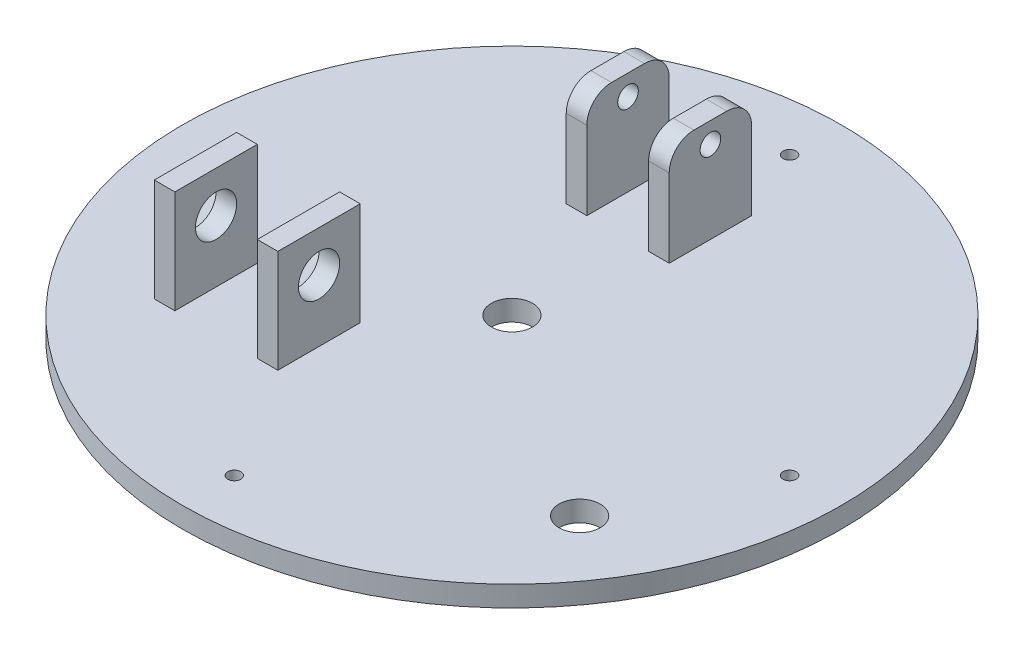
SolidWorks part; units mm, degrees
material "6061 Alloy"
ref_plane "Front Plane" through (0, 0, 0) normal (0, 0, 1) x (1, 0, 0)
ref_plane "Top Plane" through (0, 0, 0) normal (0, 1, 0) x (1, 0, 0)
ref_plane "Right Plane" through (0, 0, 0) normal (1, 0, 0) x (0, 0, -1)
sketch "Sketch1" plane through (0, 0, 0) normal (0, 1, 0) x (1, 0, 0)
  circle A0 centre (0, 0) radius 101.6
  dimension "D1" = 203.2
extrude "Boss-Extrude1" add sketch "Sketch1" along normal blind 6.35
sketch "Sketch2" plane through (0, 0, 0) normal (0, -1, 0) x (1, 0, 0)
  circle A0 centre (0, 0) radius 6.35
  dimension "D1" = 12.7
extrude "Cut-Extrude1" cut sketch "Sketch2" against normal through all
sketch "Sketch3" plane through (0, 6.35, 0) normal (0, 1, 0) x (1, 0, 0)
  line L0 (-53.1127, -38.1) -> (-27.7127, -38.1) construction
  line L1 (-59.4627, -25.4) -> (-53.1127, -25.4)
  line L2 (-59.4627, -25.4) -> (-59.4627, -50.8)
  line L3 (-59.4627, -50.8) -> (-53.1127, -50.8)
  line L4 (-53.1127, -25.4) -> (-53.1127, -50.8)
  line L5 (-27.7127, -25.4) -> (-21.3627, -25.4)
  line L6 (-27.7127, -25.4) -> (-27.7127, -50.8)
  line L7 (-27.7127, -50.8) -> (-21.3627, -50.8)
  line L8 (-21.3627, -25.4) -> (-21.3627, -50.8)
  point P10 (-40.4127, -38.1)
  dimension "D1" = 40.4127
  dimension "D2" = 6.35
  dimension "D3" = 38.1
  dimension "D4" = 25.4
  dimension "D5" = 25.4
extrude "Boss-Extrude2" add sketch "Sketch3" along normal blind 31.75
sketch "Sketch4" plane through (-21.3627, 0, 0) normal (1, 0, 0) x (0, 0, -1)
  line L0 (-38.1, 38.1) -> (-38.1, 25.4) construction
  line L1 (-50.8, 38.1) -> (-25.4, 38.1) construction
  circle A0 centre (-38.1, 25.4) radius 6.35
  dimension "D1" = 12.7
  dimension "D2" = 12.7
extrude "Cut-Extrude2" cut sketch "Sketch4" against normal up to surface (38.1 mm away) up to face at (-59.4627, 22.225, 38.1)
sketch "Sketch5" plane through (0, 6.35, 0) normal (0, 1, 0) x (1, 0, 0)
  line L0 (-15.0127, 50.8) -> (4.0373, 50.8) construction
  line L2 (-21.3627, 38.1) -> (-15.0127, 38.1)
  line L3 (-21.3627, 38.1) -> (-21.3627, 63.5)
  line L4 (-21.3627, 63.5) -> (-15.0127, 63.5)
  line L5 (-15.0127, 38.1) -> (-15.0127, 63.5)
  line L6 (4.0373, 63.5) -> (10.3873, 63.5)
  line L7 (4.0373, 63.5) -> (4.0373, 38.1)
  line L8 (4.0373, 38.1) -> (10.3873, 38.1)
  line L9 (10.3873, 63.5) -> (10.3873, 38.1)
  point P10 (-5.4877, 50.8)
  dimension "D1" = 25.4
  dimension "D2" = 6.35
  dimension "D3" = 19.05
  dimension "D4" = 34.925
  dimension "D5" = 88.9
extrude "Boss-Extrude3" add sketch "Sketch5" along normal blind 31.75
sketch "Sketch6" plane through (-21.3627, 0, 0) normal (-1, 0, 0) x (0, 0, 1)
  line L0 (-50.8, 38.1) -> (-50.8, 31.75) construction
  line L1 (-63.5, 38.1) -> (-38.1, 38.1) construction
  circle A0 centre (-50.8, 31.75) radius 3.175
  dimension "D1" = 6.35
  dimension "D2" = 6.35
extrude "Cut-Extrude3" cut sketch "Sketch6" against normal up to surface (31.75 mm away) up to face at (10.3873, 22.225, -50.8)
hole_wizard "#10-32 Tapped Hole1" positions "Sketch8" profile "Sketch7" tap size "#10-32" standard "ANSI Inch"
sketch "Sketch8" plane through (0, 0, 0) normal (0, -1, 0) x (-1, 0, 0)
  line L1 (85.5998, 0) -> (0, 85.5998)
  line L2 (85.5998, 0) -> (0, -85.5998)
  line L3 (0, 85.5998) -> (-85.5998, 0)
  line L4 (0, -85.5998) -> (-85.5998, 0)
  line L5 (85.5998, 0) -> (-85.5998, 0) construction
  line L6 (0, 85.5998) -> (0, -85.5998) construction
  point P252 (0, 0)
  point P331 (0, -85.5998)
  point P333 (-85.5998, 0)
  point P335 (0, 85.5998)
  point P337 (85.5998, 0)
  dimension "D1" = 121.0564
sketch "Sketch7" plane through (0, 0, 0) normal (1, 0, 0) x (0, 0, -1)
  line L0 (0, 0) -> (0, 13.2428)
  line L1 (0, 13.2428) -> (2.0193, 12.0294)
  line L2 (2.0193, 12.0294) -> (2.0193, 0)
  line L5 (2.0193, 0) -> (0, 0)
  line L10 (0, 13.2428) -> (-2.0193, 12.0294) construction
  line L11 (0, -6.35) -> (0, 107.95) construction
  dimension "Tap Drill Dia." = 4.0386
  dimension "Tap Drill Depth" = 12.0294
  dimension "Drill Angle" = 118
fillet "Fillet1" radius 7.62 4 edges at (7.2123, 38.1, -38.1) (-18.1877, 38.1, -38.1) (-18.1877, 38.1, -63.5) (7.2123, 38.1, -63.5)
sketch "Sketch9" plane through (0, 6.35, 0) normal (0, 1, 0) x (1, 0, 0)
  line L0 (0, 0) -> (84.2496, -56.7852) construction
  line L1 (0, 0) -> (64.0297, -43.1568) construction
  circle A0 centre (0, 0) radius 101.6 construction
  circle A1 centre (64.0297, -43.1568) radius 6.35
  dimension "D2" = 12.7
  dimension "D1" = 77.216
extrude "Cut-Extrude4" cut sketch "Sketch9" against normal through all
